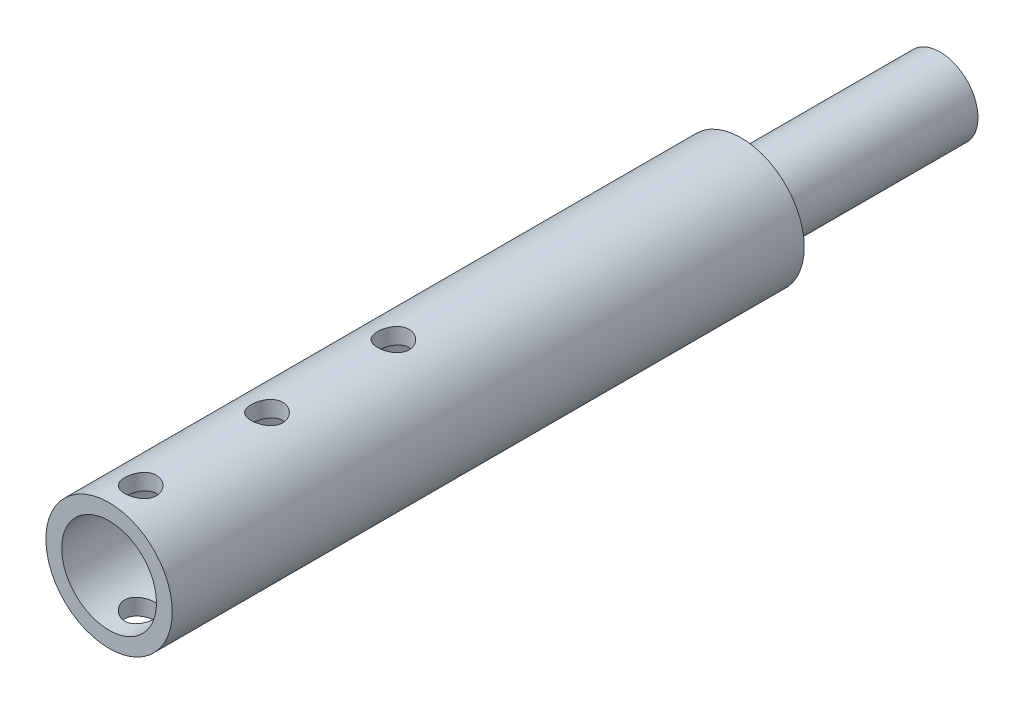
SolidWorks part; units mm, degrees
ref_plane "Płaszczyzna przednia" through (0, 0, 0) normal (0, 0, 1) x (1, 0, 0)
ref_plane "Płaszczyzna górna" through (0, 0, 0) normal (0, 1, 0) x (1, 0, 0)
ref_plane "Płaszczyzna prawa" through (0, 0, 0) normal (1, 0, 0) x (0, 0, -1)
sketch "Szkic1" plane through (0, 0, 0) normal (0, 0, 1) x (1, 0, 0)
  circle A0 centre (0, 0) radius 6
  circle A1 centre (0, 0) radius 12
extrude "Dodanie-wyciągnięcie1" add sketch "Szkic1" along normal blind 40
sketch "Szkic2" plane through (0, 0, 40) normal (0, 0, 1) x (1, 0, 0)
  circle A0 centre (0, 0) radius 12
extrude "Dodanie-wyciągnięcie2" add sketch "Szkic2" along normal blind 23
sketch "Szkic3" plane through (0, 0, 63) normal (0, 0, 1) x (1, 0, 0)
  circle A0 centre (0, 0) radius 20
extrude "Dodanie-wyciągnięcie3" add sketch "Szkic3" along normal blind 200
sketch "Szkic4" plane through (0, 0, 263) normal (0, 0, 1) x (1, 0, 0)
  circle A0 centre (0, 0) radius 15
extrude "Wytnij-wyciągnięcie1" cut sketch "Szkic4" against normal blind 150
sketch "Szkic5" plane through (0, 0, 0) normal (0, 1, 0) x (1, 0, 0)
  circle A0 centre (0, -333.025) radius 5
  circle A1 centre (0, -293.025) radius 5
  circle A2 centre (0, -253.025) radius 5
  circle A3 centre (0, -213.025) radius 5
  circle A4 centre (0, -173.025) radius 5
  dimension "D1" = 5
extrude "Wytnij-wyciągnięcie2" cut sketch "Szkic5" against normal blind 250 and the other way blind 250
